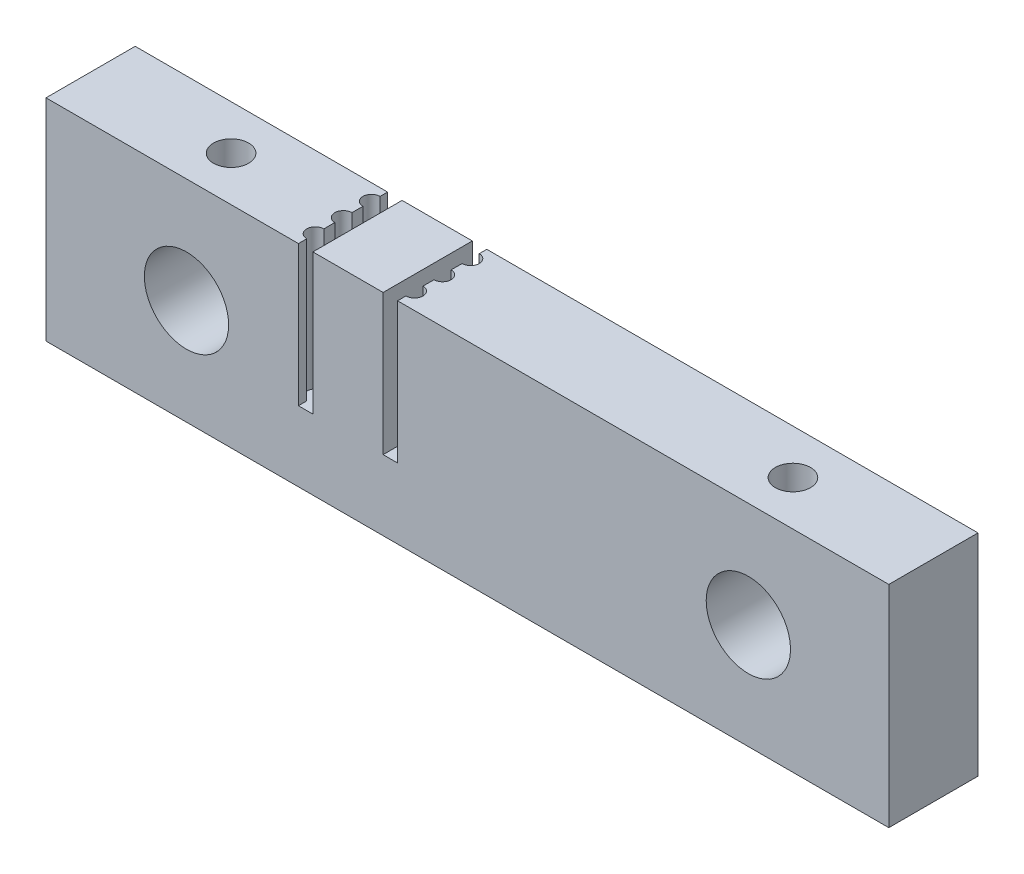
SolidWorks part; units mm, degrees
material "6061 Alloy"
ref_plane "Front Plane" through (0, 0, 0) normal (0, 0, 1) x (1, 0, 0)
ref_plane "Top Plane" through (0, 0, 0) normal (0, 1, 0) x (1, 0, 0)
ref_plane "Right Plane" through (0, 0, 0) normal (1, 0, 0) x (0, 0, -1)
sketch "Sketch1" plane through (0, 0, 0) normal (0, 0, 1) x (1, 0, 0)
  line L0 (30, 15) -> (30, 0) construction
  line L1 (0, 0) -> (60, 0)
  line L2 (0, 0) -> (0, 15)
  line L3 (0, 15) -> (60, 15)
  line L4 (60, 0) -> (60, 15)
  line L5 (0, 7.5) -> (60, 7.5) construction
  circle A0 centre (10, 7.5) radius 3
  circle A1 centre (50, 7.5) radius 3
  dimension "D3" = 6
  dimension "D1" = 60
  dimension "D2" = 15
  dimension "D4" = 40
extrude "Boss-Extrude1" add sketch "Sketch1" along normal blind 6.35
ref_axis "Axis1" through (10, 7.5, 6.35) along (0, 0, -1)
hole_wizard "M3 Tapped Hole1" positions "Sketch4" profile "Sketch3" tap size "M3" standard "ISO"
sketch "Sketch4" plane through (0, 15, 0) normal (0, 1, 0) x (-1, 0, 0)
  line L0 (0, 3.175) -> (-60, 3.175) construction
  line L1 (0, 6.35) -> (0, 0) construction
  line L2 (-60, 6.35) -> (-60, 0) construction
  line L5 (-30, 0) -> (-30, 6.35) construction
  line L6 (-60, 0) -> (0, 0) construction
  line L7 (-60, 6.35) -> (0, 6.35) construction
  line L10 (-10, 6.35) -> (-10, 0) construction
  point P0 (-10, 3.175)
  point P25 (-50, 3.175)
sketch "Sketch3" plane through (10, 15, 3.175) normal (1, 0, 0) x (0, 0, 1)
  line L0 (0, 0) -> (0, 9.2511)
  line L1 (0, 9.2511) -> (1.25, 8.5)
  line L2 (1.25, 8.5) -> (1.25, 0)
  line L5 (1.25, 0) -> (0, 0)
  line L10 (0, 9.2511) -> (-1.25, 8.5) construction
  line L11 (0, -6.35) -> (0, 107.95) construction
  dimension "Tap Drill Dia." = 2.5
  dimension "Tap Drill Depth" = 8.5
  dimension "Drill Angle" = 118
cosmetic thread "Hole Thread1" parameters "D1"=4.8642, "D2"=3
cosmetic thread "Hole Thread2" parameters "D1"=4.8642, "D2"=3
ref_plane "Center plane" through (30, 0, 0) normal (-1, 0, 0) x (0, 0, 1)
ref_plane "Belt plane" through (19, 0, 0) normal (-1, 0, 0) x (0, 0, 1)
sketch "Sketch5" plane through (0, 15, 0) normal (0, 1, 0) x (1, 0, 0)
  line L0 (19, -6.35) -> (19, 0) construction
  line L1 (60, -6.35) -> (0, -6.35) construction
  line L2 (60, 0) -> (0, 0) construction
  line L3 (19, -6.35) -> (19, 0)
  line L4 (19, 0) -> (17.97, 0)
  line L5 (17.97, 0) -> (17.97, -0.5375)
  line L6 (17.97, -1.7575) -> (17.97, -2.5375)
  line L7 (17.97, -3.7575) -> (17.97, -4.5375)
  line L8 (17.97, -5.7575) -> (17.97, -6.35)
  line L9 (17.97, -6.35) -> (19, -6.35)
  line L10 (25.03, -6.35) -> (24, -6.35)
  line L11 (30, 3.4925) -> (30, -3.4925) construction
  line L12 (21.5, 0) -> (21.5, -6.35) construction
  line L13 (25.03, -5.7575) -> (25.03, -6.35)
  line L14 (25.03, -3.7575) -> (25.03, -4.5375)
  line L15 (25.03, -1.7575) -> (25.03, -2.5375)
  line L16 (25.03, 0) -> (25.03, -0.5375)
  line L17 (24, 0) -> (25.03, 0)
  line L18 (24, -6.35) -> (24, 0)
  arc A0 (25.03, -4.5375) -> (25.03, -5.7575) centre (25.03, -5.1475) cw
  arc A1 (25.03, -2.5375) -> (25.03, -3.7575) centre (25.03, -3.1475) cw
  arc A2 (25.03, -0.5375) -> (25.03, -1.7575) centre (25.03, -1.1475) cw
  arc A3 (17.97, -0.5375) -> (17.97, -1.7575) centre (17.97, -1.1475) ccw
  arc A4 (17.97, -2.5375) -> (17.97, -3.7575) centre (17.97, -3.1475) ccw
  arc A5 (17.97, -4.5375) -> (17.97, -5.7575) centre (17.97, -5.1475) ccw
  dimension "D1" = 2
  dimension "D4" = 0.61
  dimension "D2" = 2
  dimension "D3" = 1.03
  dimension "D5" = 11
  dimension "D6" = 5
extrude "Cut-Extrude1" cut sketch "Sketch5" against normal blind 10
